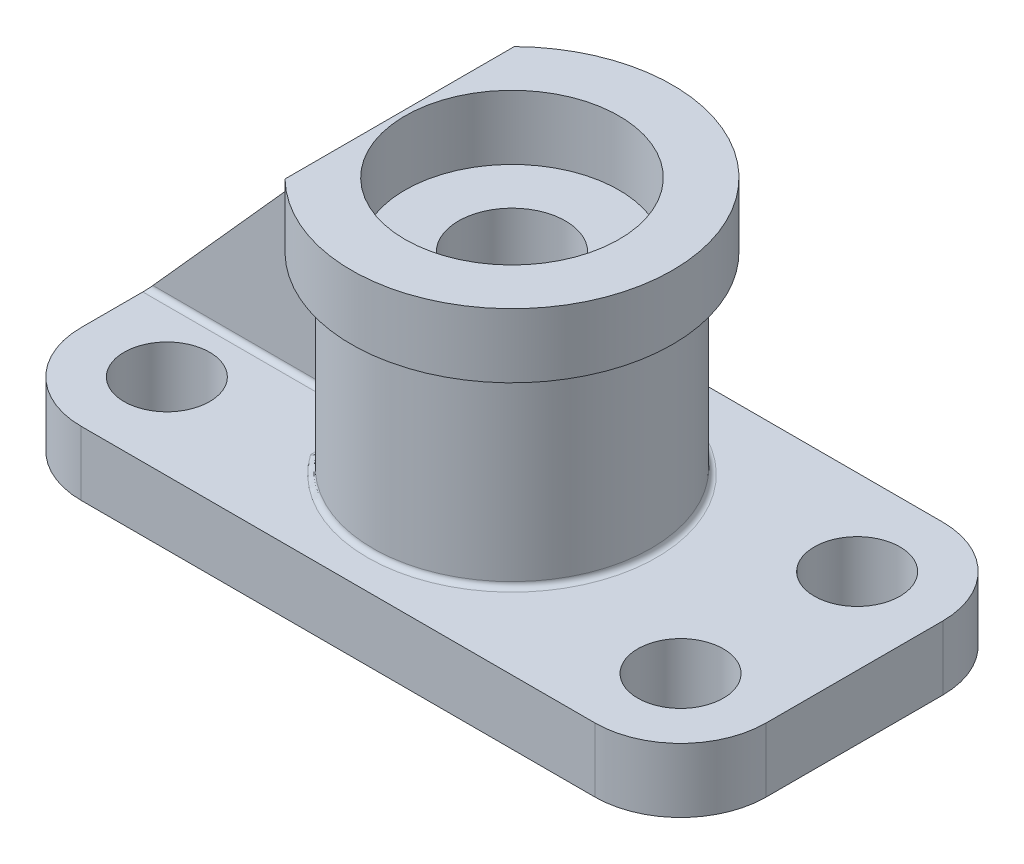
SolidWorks part; units mm, degrees
ref_plane "Ön Düzlem" through (0, 0, 0) normal (0, 0, 1) x (1, 0, 0)
ref_plane "Üst Düzlem" through (0, 0, 0) normal (0, 1, 0) x (1, 0, 0)
ref_plane "Sağ Düzlem" through (0, 0, 0) normal (1, 0, 0) x (0, 0, -1)
sketch "Çizim1" plane through (0, 0, 0) normal (0, 1, 0) x (1, 0, 0)
  line L1 (48, -32.5) -> (-48, -32.5)
  line L2 (64, -16.5) -> (64, 16.5)
  line L3 (48, 32.5) -> (-48, 32.5)
  line L4 (-64, -16.5) -> (-64, 16.5)
  line L5 (64, -32.5) -> (-64, 32.5) construction
  line L6 (64, 32.5) -> (-64, -32.5) construction
  arc A0 (-48, -32.5) -> (-64, -16.5) centre (-48, -16.5) cw
  arc A1 (48, -32.5) -> (64, -16.5) centre (48, -16.5) ccw
  arc A2 (64, 16.5) -> (48, 32.5) centre (48, 16.5) ccw
  arc A3 (-48, 32.5) -> (-64, 16.5) centre (-48, 16.5) ccw
  circle A4 centre (-48, 16.5) radius 8
  circle A5 centre (-48, -16.5) radius 8
  circle A6 centre (48, 16.5) radius 8
  circle A7 centre (48, -16.5) radius 8
  point P0 (0, 0)
  dimension "D3" = 16
  dimension "D4" = 16
  dimension "D5" = 16
  dimension "D6" = 16
  dimension "D7" = 16
  dimension "D1" = 65
  dimension "D2" = 128
extrude "Yükseklik-Ekstrüzyon1" add sketch "Çizim1" along normal blind 12
sketch "Çizim2" plane through (0, 12, 0) normal (0, 1, 0) x (1, 0, 0)
  circle A0 centre (0, 0) radius 26
  circle A1 centre (0, 0) radius 10
extrude "Yükseklik-Ekstrüzyon2" add sketch "Çizim2" along normal blind 36
sketch "Çizim3" plane through (0, 48, 0) normal (0, 1, 0) x (1, 0, 0)
  circle A0 centre (0, 0) radius 10
extrude "Kes-Ekstrüzyon1" cut sketch "Çizim3" against normal through all
sketch "Çizim4" plane through (0, 48, 0) normal (0, 1, 0) x (1, 0, 0)
  circle A0 centre (0, 0) radius 30
  circle A1 centre (0, 0) radius 20
extrude "Yükseklik-Ekstrüzyon3" add sketch "Çizim4" along normal blind 12
sketch "Çizim8" plane through (0, 60, 0) normal (0, 1, 0) x (1, 0, 0)
  line L1 (-36.018, 28.0544) -> (-21, 28.0544)
  line L2 (-36.018, 28.0544) -> (-36.018, -30.766)
  line L3 (-36.018, -30.766) -> (-21, -30.766)
  line L4 (-21, 28.0544) -> (-21, -30.766)
  dimension "D1" = 21
extrude "Kes-Ekstrüzyon5" cut sketch "Çizim8" against normal up to surface (48 mm away) up to face at (0, 12, -26)
sketch "Çizim9" plane through (0, 0, 0) normal (0, 0, 1) x (1, 0, 0)
  line L0 (-21, 60) -> (-64, 12)
  point P3 (0, 0)
  point P4 (0, 0)
  point P6 (0, 0)
  point P7 (0, 0)
  point P8 (0, 0)
  point P10 (0, 0)
rib "Feder1" sketch "Çizim9" sketch "Çizim9" thickness 8 extrusion direction parallel to sketch draft on no parameters "D1"=8
fillet "Radyus1" radius 1 7 edges at (-21, 36, -4) (-21, 12, -9.6649) (-42.5, 12, -4) (-42.5, 12, 4) (-21, 12, 9.6649) (26, 12, 0) (-21, 36, 4)
